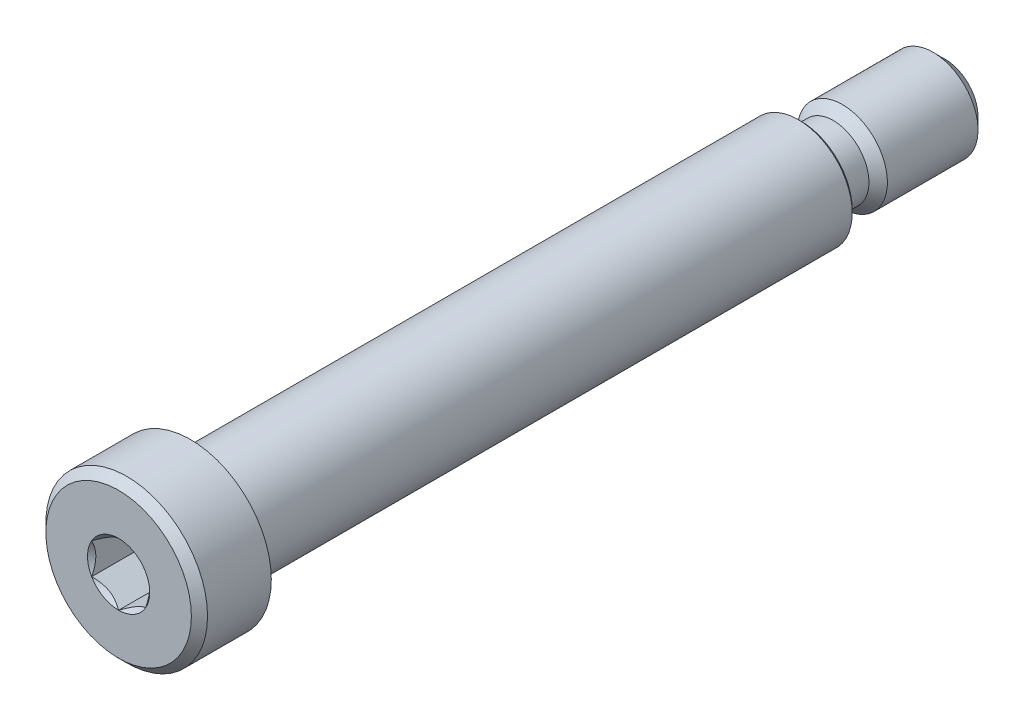
SolidWorks part; units mm, degrees
material "Alloy Steel"
ref_plane "Front Plane" through (0, 0, 0) normal (0, 0, 1) x (1, 0, 0)
ref_plane "Top Plane" through (0, 0, 0) normal (0, 1, 0) x (1, 0, 0)
ref_plane "Right Plane" through (0, 0, 0) normal (1, 0, 0) x (0, 0, -1)
sketch "Sketch2" plane through (0, 0, 0) normal (1, 0, 0) x (0, 0, -1)
  line L0 (-36.5125, 0) -> (36.5125, 0) construction
  line L1 (-36.5125, 0) -> (-36.5125, 7.1437)
  line L2 (-36.5125, 7.1437) -> (-30.1625, 7.1437)
  line L3 (-30.1625, 7.1437) -> (-30.1625, 4.7625)
  line L4 (-30.1625, 4.7625) -> (23.8125, 4.7625)
  line L5 (23.8125, 3.9751) -> (36.5125, 3.9751)
  line L6 (36.5125, 3.9751) -> (36.5125, 0)
  line L7 (36.4243, 4.1279) -> (37.1299, 2.9058) construction
  line L8 (37.1299, 2.9058) -> (37.8354, 4.1279) construction
  line L9 (37.8354, 4.1279) -> (36.4243, 4.1279) construction
  line L10 (36.5125, 3.9751) -> (37.7472, 3.9751) construction
  line L11 (37.1299, 4.1279) -> (37.1299, 3.9751) construction
  line L12 (37.1299, 3.9751) -> (37.1299, 3.0586) construction
  line L13 (37.1299, 3.0586) -> (37.1299, 2.9058) construction
  line L14 (37.0417, 3.0586) -> (37.2181, 3.0586)
  line L15 (36.4684, 4.0515) -> (37.7913, 4.0515)
  line L16 (37.2181, 3.0586) -> (37.7913, 4.0515)
  line L17 (37.0417, 3.0586) -> (36.4684, 4.0515)
  line L18 (36.5125, 0) -> (36.5125, -3.9751) construction
  line L19 (23.8125, -4.7625) -> (23.8125, 0) construction
  line L20 (23.8125, 0) -> (23.8125, 4.7625) construction
  line L21 (-36.5125, 0) -> (-36.5125, -7.1437) construction
  point P12 (32.9847, -3.9751)
  point P22 (37.1299, 4.0515)
  point P23 (21.2725, 0)
  point P25 (-21.2725, 0)
  point P26 (-30.1625, -7.1437)
  point P29 (23.8125, -4.7625)
  dimension "Head Height" = 6.35
  dimension "Shoulder Diameter" = 9.525
  dimension "Screw Size Decimal Equivalent" = 7.9502
  dimension "Thread Length" = 12.7
  dimension "Head Diameter" = 14.2875
  dimension "Pitch" = 1.4111
  dimension "D2" = 0.1764
  dimension "D1" = 3.5278
  dimension "D3" = 15.24
  dimension "D4" = 15.24
  dimension "Shoulder Length" = 53.975
sketch "Sketch3" plane through (0, 0, 0) normal (0, 0, 1) x (1, 0, 0)
  line L1 (0, 2.7496) -> (-2.3813, 1.3748)
  line L2 (-2.3813, 1.3748) -> (-2.3813, -1.3748)
  line L3 (-2.3813, -1.3748) -> (0, -2.7496)
  line L4 (0, -2.7496) -> (2.3812, -1.3748)
  line L5 (2.3812, -1.3748) -> (2.3812, 1.3748)
  line L6 (2.3812, 1.3748) -> (0, 2.7496)
  circle A0 centre (0, 0) radius 2.3813 construction
  dimension "Drive Size" = 4.7625
sketch "Sketch4" plane through (0, 0, 0) normal (1, 0, 0) x (0, 0, -1)
  line L0 (-30.1625, 7.1437) -> (-35.7981, 7.1437)
  line L1 (-35.7981, 7.1437) -> (-36.5125, 6.4294)
  line L2 (-30.1625, 7.1437) -> (-30.1625, 4.7625)
  line L7 (-36.5125, 0) -> (36.5125, 0) construction
  line L8 (-30.1625, 4.7625) -> (23.55, 4.7625)
  line L9 (23.55, 4.7625) -> (23.8125, 4.5)
  line L10 (23.8125, 4.5) -> (23.8125, 0)
  line L11 (23.8125, 4.7625) -> (23.8125, 4.5) construction
  line L12 (23.8125, 4.5) -> (23.8125, 4.2376) construction
  line L13 (23.8125, 4.2376) -> (23.8125, 3.9751) construction
  line L14 (-36.5125, 6.4294) -> (-36.5125, 0)
  line L16 (-36.5125, 0) -> (23.8125, 0)
  line L18 (-36.5125, 7.1437) -> (-30.1625, 7.1437) construction
  dimension "D3" = 45
  dimension "D5" = 12.8587
  dimension "D1" = 45
revolve "Revolve1" add sketch "Sketch4" angle 360 about L16
sketch "Sketch5" plane through (0, 0, 36.5125) normal (0, 0, 1) x (1, 0, 0)
  line L0 (2.3812, 1.3748) -> (0, 2.7496) construction
  line L1 (2.3812, -1.3748) -> (2.3812, 1.3748) construction
  line L2 (0, -2.7496) -> (2.3812, -1.3748) construction
  line L3 (-2.3813, -1.3748) -> (0, -2.7496) construction
  line L4 (-2.3813, 1.3748) -> (-2.3813, -1.3748) construction
  line L5 (0, 2.7496) -> (-2.3813, 1.3748) construction
  line L6 (2.3812, 1.3748) -> (0, 2.7496)
  line L7 (2.3812, -1.3748) -> (2.3812, 1.3748)
  line L8 (0, -2.7496) -> (2.3812, -1.3748)
  line L9 (-2.3813, -1.3748) -> (0, -2.7496)
  line L10 (-2.3813, 1.3748) -> (-2.3813, -1.3748)
  line L11 (0, 2.7496) -> (-2.3813, 1.3748)
extrude "Cut-Extrude1" cut sketch "Sketch5" against normal blind 4.7625
sketch "Sketch6" plane through (0, 0, 36.5125) normal (0, 0, 1) x (1, 0, 0)
  circle A0 centre (0, 0) radius 2.7496
extrude "Cut-Extrude4" cut sketch "Sketch6" against normal blind 4.7625 draft 45
sketch "Sketch7" plane through (0, 0, 0) normal (1, 0, 0) x (0, 0, -1)
  line L0 (23.8125, 3.9751) -> (35.4542, 3.9751)
  line L1 (23.8125, 3.9751) -> (36.5125, 3.9751) construction
  line L2 (35.4542, 3.9751) -> (36.5125, 2.9168)
  line L3 (36.5125, 3.9751) -> (36.5125, 0) construction
  line L4 (36.5125, 2.9168) -> (36.5125, 0)
  line L5 (36.5125, 0) -> (23.8125, 0)
  line L6 (23.8125, -4.5) -> (23.8125, 4.5) construction
  line L7 (23.8125, 0) -> (23.8125, 3.9751)
  dimension "D1" = 45
  dimension "D2" = 1.0583
revolve "Revolve2" add sketch "Sketch7" angle 360 about L5
sketch "Sketch10" plane through (0, 0, 0) normal (1, 0, 0) x (0, 0, -1)
  line L0 (24.6253, 3.1623) -> (26.6319, 3.1623)
  line L1 (26.6319, 3.1623) -> (28.2321, 4.7625)
  line L2 (28.2321, 4.7625) -> (23.8125, 4.7625)
  line L3 (23.8125, 4.7625) -> (23.8125, 3.9751)
  line L4 (23.8125, -4.5) -> (23.8125, 4.5) construction
  line L5 (36.5125, 0) -> (23.8125, 0) construction
  line L6 (-36.5125, 0) -> (36.5125, 0) construction
  arc A0 (23.8125, 3.9751) -> (24.6253, 3.1623) centre (24.6253, 3.9751) ccw
  dimension "Flat OD" = 6.3246
  dimension "Flat" = 2.8194
  dimension "D3" = 45
revolve "Cut-Revolve1" cut sketch "Sketch10" angle 360 about L5
sketch "Sketch8" [suppressed] plane through (0, 0, -36.5125) normal (0, 0, -1) x (-1, 0, 0)
  circle A0 centre (0, 0) radius 3.9751 construction
  circle A1 centre (0, 0) radius 3.9751
curve "Helix/Spiral1" [suppressed] pitch 1.4111 height 14.1111 turns 10
sketch "Sketch9" [suppressed] plane through (0, 0, 0) normal (1, 0, 0) x (0, 0, -1)
  line L0 (37.0417, 3.0586) -> (37.2181, 3.0586) construction
  line L1 (37.2181, 3.0586) -> (37.7913, 4.0515) construction
  line L2 (36.4684, 4.0515) -> (37.7913, 4.0515) construction
  line L3 (37.0417, 3.0586) -> (36.4684, 4.0515) construction
  line L4 (37.0417, 3.0586) -> (37.2181, 3.0586)
  line L5 (37.2181, 3.0586) -> (37.7913, 4.0515)
  line L6 (36.4684, 4.0515) -> (37.7913, 4.0515)
  line L7 (37.0417, 3.0586) -> (36.4684, 4.0515)
ref_plane "Plane1" [suppressed] through (0, 0, -26.6319) normal (0, 0, 1) x (1, 0, 0)
split "Split1" [suppressed] bodies to split 138
sweep "Cut-Sweep1" [suppressed] cut profiles "Sketch9" path "Helix/Spiral1"
combine bodies "Combine1" [suppressed] operation type add bodies to combine 141 139
sketch "Sketch11" [suppressed] plane through (0, 0, 36.5125) normal (0, 0, 1) x (1, 0, 0)
  line L0 (-0.1031, 7.1438) -> (0.1031, 7.1438)
  line L1 (0.1031, 7.1438) -> (0, 6.9652)
  line L2 (0, 0) -> (0, 7.1437) construction
  line L3 (0, 6.9652) -> (-0.1031, 7.1438)
  line L4 (0, 0) -> (7.1437, 0) construction
  circle A0 centre (0, 0) radius 7.1437 construction
  point P6 (0, 7.1438)
  dimension "D1" = 13.9303
  dimension "D2" = 60
  dimension "D3" = 0.2062
sketch "Sketch12" [suppressed] plane through (0, 0, 0) normal (1, 0, 0) x (0, 0, -1)
  line L0 (-36.5125, 6.9652) -> (-32.1812, 6.9652)
  line L1 (-31.5714, 7.5749) -> (-31.5714, 7.1437) construction
  line L2 (-36.5125, 7.1437) -> (-30.1625, 7.1437) construction
  arc A0 (-32.1812, 6.9652) -> (-31.5714, 7.5749) centre (-32.1812, 7.5749) ccw
  point P11 (-31.75, 7.1437)
  dimension "D1" = 1.5875
sweep "Cut-Sweep2" [suppressed] cut profiles "Sketch11" path "Sketch12"
pattern_circular "CirPattern1" [suppressed] count 76 over 360 about axis through (0, 0, 36.5125) along (0, 0, -1) of bodies 143
equation "\"D2@Sketch2\" = \"Pitch@Sketch2\" / 8"
equation "\"D1@Sketch2\"=\"Pitch@Sketch2\"*2.5"
equation "\"D5@Sketch4\"=\"Head Diameter@Sketch2\"*0.9"
equation "\"D1@Cut-Extrude1\"=\"Head Height@Sketch2\"*0.75"
equation "\"D1@Cut-Extrude4\"=\"D1@Cut-Extrude1\""
equation "\"D2@Sketch7\"=\"pitch@sketch2\"*0.75"
equation "\"D3@Helix/Spiral1\"=\"Thread Length@Sketch2\"+\"Pitch@Sketch2\""
equation "\"D4@Helix/Spiral1\"=\"Pitch@Sketch2\""
equation "\"D1@Sketch11\"=\"Head Diameter@Sketch2\"*0.975"
equation "\"D1@Sketch12\"=\"Head Height@Sketch2\"*0.25"
equation "\"D1@CirPattern1\"=\"Head Diameter@Sketch2\" * 3.14 / \"D3@Sketch11\" * 0.35"
equation "\"D3@Sketch2\"=\"Thread Length@Sketch2\"*1.2"
equation "\"D4@Sketch2\"=\"D3@Sketch2\""
